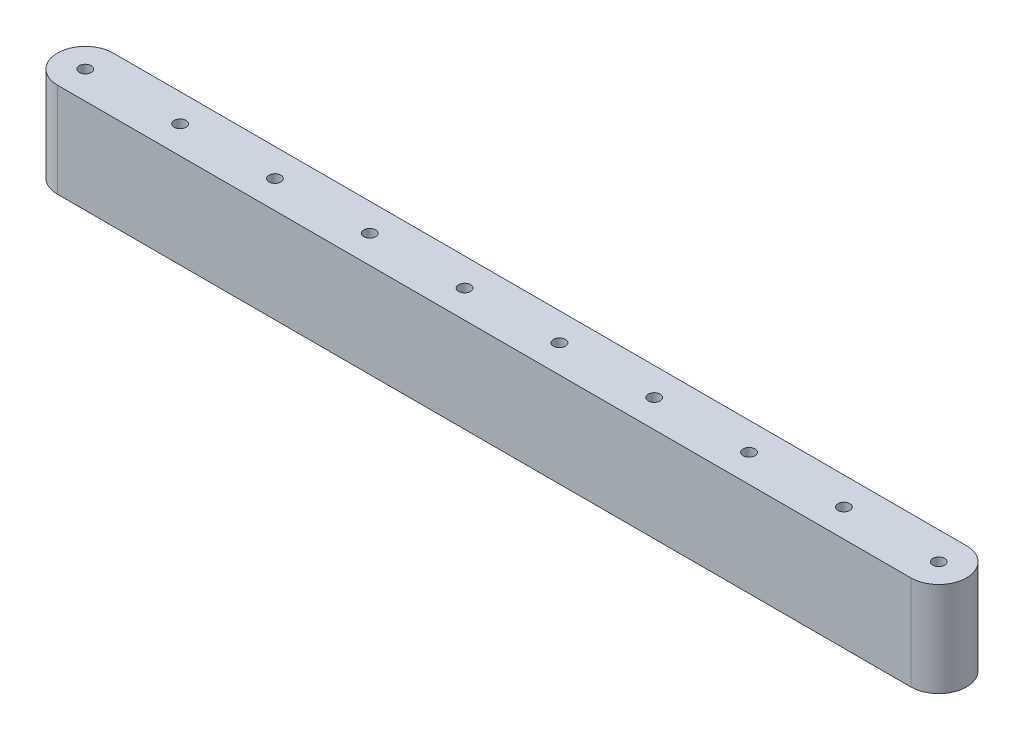
SolidWorks part; units mm, degrees
ref_plane "Front Plane" through (0, 0, 0) normal (0, 0, 1) x (1, 0, 0)
ref_plane "Top Plane" through (0, 0, 0) normal (0, 1, 0) x (1, 0, 0)
ref_plane "Right Plane" through (0, 0, 0) normal (1, 0, 0) x (0, 0, -1)
sketch "Sketch1" plane through (0, 0, 0) normal (0, 1, 0) x (1, 0, 0)
  line L0 (-73.025, 0) -> (73.025, 0) construction
  line L1 (-73.025, 4.7625) -> (73.025, 4.7625)
  line L2 (-73.025, -4.7625) -> (73.025, -4.7625)
  arc A0 (-73.025, 4.7625) -> (-73.025, -4.7625) centre (-73.025, 0) ccw
  arc A1 (73.025, -4.7625) -> (73.025, 4.7625) centre (73.025, 0) ccw
  point P2 (0, 0)
  dimension "D3" = 9.525
  dimension "D1" = 146.05
extrude "Boss-Extrude1" add sketch "Sketch1" along normal mid plane 16.175
sketch "Sketch2" plane through (0, 0, 0) normal (0, 1, 0) x (1, 0, 0)
  circle A0 centre (-73.025, 0) radius 1.016
  circle A1 centre (-56.7972, 0) radius 1.016
  circle A2 centre (-40.5694, 0) radius 1.016
  circle A3 centre (-24.3417, 0) radius 1.016
  circle A4 centre (-8.1139, 0) radius 1.016
  circle A5 centre (8.1139, 0) radius 1.016
  circle A6 centre (24.3417, 0) radius 1.016
  circle A7 centre (40.5694, 0) radius 1.016
  circle A8 centre (56.7972, 0) radius 1.016
  circle A9 centre (73.025, 0) radius 1.016
  arc A11 (73.025, -4.7625) -> (73.025, 4.7625) centre (73.025, 0) ccw construction
  dimension "D1" = 2.032
  dimension "D2" = 10
extrude "Cut-Extrude1" cut sketch "Sketch2" against normal through all both and the other way through all
equation "\"Num_Holes\"=10"
equation "\"D1@LPattern1\"=\"Num_Holes\""
